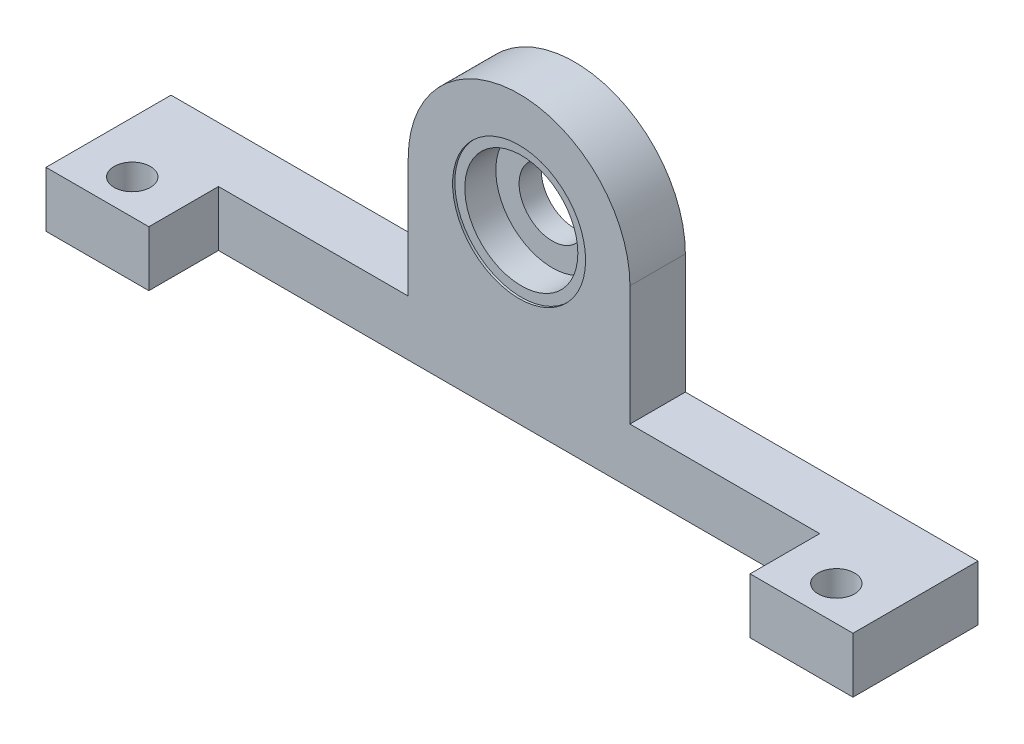
SolidWorks part; units mm, degrees
ref_plane "Front Plane" through (0, 0, 0) normal (0, 0, 1) x (1, 0, 0)
ref_plane "Top Plane" through (0, 0, 0) normal (0, 1, 0) x (1, 0, 0)
ref_plane "Right Plane" through (0, 0, 0) normal (1, 0, 0) x (0, 0, -1)
sketch "Sketch1" plane through (0, 0, 0) normal (0, 0, 1) x (1, 0, 0)
  line L0 (-12.7, 0) -> (-12.7, -13.716)
  line L1 (-12.7, -13.716) -> (-46.228, -13.716)
  line L2 (-46.228, -13.716) -> (-46.228, -20.066)
  line L3 (0, 0) -> (0, 22605.9957) construction
  line L4 (-46.228, -20.066) -> (46.228, -20.066)
  line L5 (46.228, -13.716) -> (46.228, -20.066)
  line L6 (12.7, -13.716) -> (46.228, -13.716)
  line L7 (12.7, 0) -> (12.7, -13.716)
  line L8 (-41.1226, -9.2487) -> (-41.1226, 49990.7513) construction
  line L9 (-36.8554, -18.7297) -> (-36.8554, 49981.2703) construction
  line L10 (-38.989, -13.9892) -> (-38.989, 49986.0108) construction
  line L12 (-41.1226, -13.716) -> (-36.8554, -13.716) construction
  line L13 (-41.1226, -13.716) -> (-41.1226, -20.066) construction
  line L14 (-41.1226, -20.066) -> (-36.8554, -20.066) construction
  line L15 (-36.8554, -13.716) -> (-36.8554, -20.066) construction
  line L16 (-41.1226, -13.716) -> (-36.8554, -20.066) construction
  line L17 (-41.1226, -20.066) -> (-36.8554, -13.716) construction
  line L18 (-42.418, -9.8692) -> (-35.56, -9.8692) construction
  line L19 (-42.418, -9.8692) -> (-42.418, -13.716) construction
  line L20 (-42.418, -13.716) -> (-35.56, -13.716) construction
  line L21 (-35.56, -9.8692) -> (-35.56, -13.716) construction
  line L22 (-42.418, -9.8692) -> (-35.56, -13.716) construction
  line L23 (-42.418, -13.716) -> (-35.56, -9.8692) construction
  circle A0 centre (0, 0) radius 3.81
  arc A1 (12.7, 0) -> (-12.7, 0) centre (0, 0) ccw
  point P6 (0, -20.066)
  point P20 (-38.989, -16.891)
  point P26 (-42.418, -11.7926)
  point P27 (-38.989, -11.7926)
  dimension "D1" = 7.62
  dimension "D2" = 12.7
  dimension "D3" = 6.35
  dimension "D4" = 20.066
  dimension "D5" = 6.858
  dimension "D6" = 4.2672
  dimension "D7" = 22.86
  dimension "D8" = 3.81
extrude "Boss-Extrude1" add sketch "Sketch1" along normal mid plane 6.35
sketch "Sketch2" plane through (0, 0, 3.175) normal (0, 0, 1) x (1, 0, 0)
  circle A0 centre (0, 0) radius 6.477
  dimension "D1" = 12.954
extrude "Cut-Extrude1" cut sketch "Sketch2" against normal blind 3.81
sketch "Sketch3" plane through (0, 0, 3.175) normal (0, 0, 1) x (1, 0, 0)
  circle A0 centre (0, 0) radius 7.62
  dimension "D1" = 15.24
extrude "Cut-Extrude2" cut sketch "Sketch3" against normal blind 0.254
sketch "Sketch6" plane through (0, 0, 3.175) normal (0, 0, 1) x (1, 0, 0)
  line L0 (-46.228, -20.066) -> (46.228, -20.066) construction
  line L1 (-46.228, -13.716) -> (-34.4424, -13.716)
  line L2 (-46.228, -13.716) -> (-46.228, -20.066)
  line L3 (-46.228, -20.066) -> (-34.4424, -20.066)
  line L4 (-34.4424, -13.716) -> (-34.4424, -20.066)
  dimension "D1" = 11.7856
extrude "Boss-Extrude2" add sketch "Sketch6" along normal blind 7.9756
sketch "Sketch7" plane through (0, -13.716, 0) normal (0, 1, 0) x (1, 0, 0)
  line L0 (-40.3352, -14.9606) -> (-40.3352, 49985.0394) construction
  line L1 (-34.4424, -11.1506) -> (-46.228, -11.1506) construction
  line L2 (-28.0924, -7.1628) -> (-50028.0924, -7.1628) construction
  line L3 (-34.4424, -11.1506) -> (-34.4424, -3.175) construction
  circle A0 centre (-40.3352, -7.1628) radius 2.0828
  point P4 (-40.3352, -11.1506)
  point P9 (-34.4424, -7.1628)
  dimension "D1" = 4.1656
extrude "Cut-Extrude4" cut sketch "Sketch7" against normal through all
mirror "Mirror2" about plane through (0, 0, 0) normal (1, 0, 0) of "Cut-Extrude4", "Boss-Extrude2"
